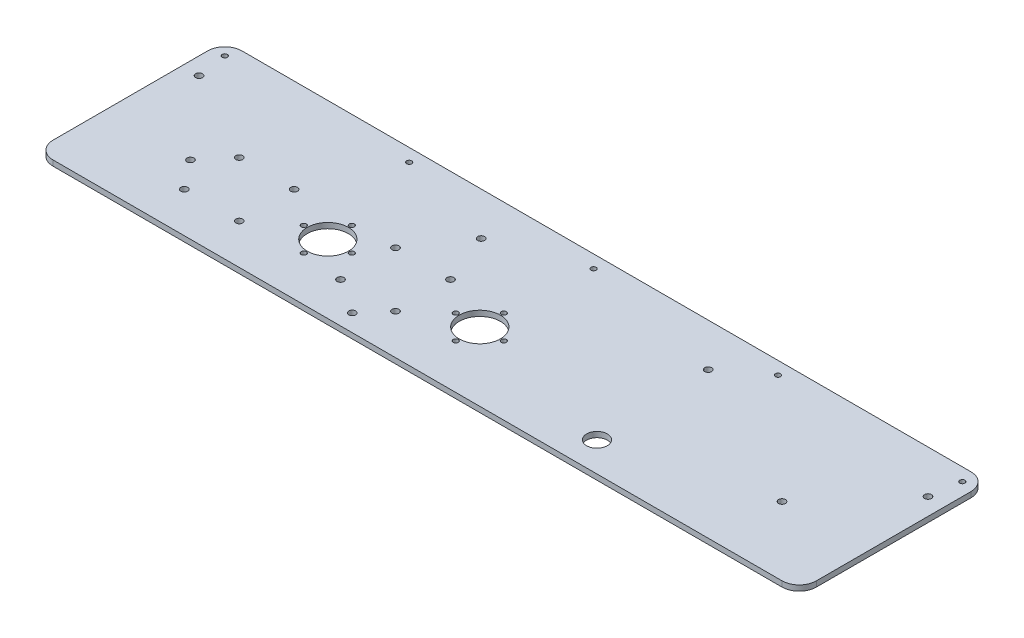
SolidWorks part; units mm, degrees
ref_plane "Front" through (0, 0, 0) normal (0, 0, 1) x (1, 0, 0)
ref_plane "Top" through (0, 0, 0) normal (0, 1, 0) x (1, 0, 0)
ref_plane "Right" through (0, 0, 0) normal (1, 0, 0) x (0, 0, -1)
sketch "Sketch1" plane through (0, 0, 0) normal (0, 1, 0) x (1, 0, 0)
  line L0 (-26.7996, 0) -> (-26.7996, 40)
  line L1 (-26.7996, 0) -> (417.7004, 0)
  line L2 (-26.7996, 0) -> (-26.7996, 110)
  line L3 (-26.7996, 110) -> (417.7004, 110)
  line L4 (417.7004, 0) -> (417.7004, 110)
  line L5 (-26.7996, 40) -> (23.2004, 40)
  line L6 (417.7004, 0) -> (417.7004, 40)
  line L7 (417.7004, 40) -> (367.7004, 40)
  line L8 (23.2004, 40) -> (103.2004, 40)
  line L9 (367.7004, 40) -> (191.7004, 40)
  line L10 (-26.7996, 110) -> (-26.7996, 85)
  line L11 (-26.7996, 85) -> (417.7004, 85)
  line L12 (-26.7996, 85) -> (-16.7996, 85)
  line L13 (417.7004, 85) -> (407.7004, 85)
  line L14 (103.2004, 40) -> (191.7004, 40)
  line L15 (147.4504, 40) -> (147.4504, 85)
  line L16 (279.7004, 40) -> (279.7004, 85)
  line L17 (147.4504, 40) -> (147.4504, 10)
  line L18 (-26.7996, 110) -> (-26.7996, 102.5)
  line L19 (-26.7996, 102.5) -> (417.7004, 102.5)
  line L20 (-26.7996, 102.5) -> (-19.2996, 102.5)
  line L21 (417.7004, 102.5) -> (410.2004, 102.5)
  line L22 (195.4504, 102.5) -> (410.2004, 102.5)
  line L23 (-19.2996, 102.5) -> (195.4504, 102.5)
  line L24 (417.7004, 0) -> (417.7004, 17.2282)
  line L25 (417.7004, 17.2282) -> (282.7004, 17.2282)
  circle A10 centre (367.7004, 40) radius 2
  circle A11 centre (23.2004, 40) radius 2
  circle A12 centre (103.2004, 40) radius 12
  circle A13 centre (103.2004, 40) radius 14
  circle A15 centre (103.2004, 54) radius 1.5
  circle A16 centre (89.2004, 40) radius 1.5
  circle A17 centre (103.2004, 26) radius 1.5
  circle A18 centre (117.2004, 40) radius 1.5
  circle A19 centre (191.7004, 40) radius 12
  circle A20 centre (191.7004, 40) radius 14
  circle A21 centre (191.7004, 26) radius 1.5
  circle A22 centre (205.7004, 40) radius 1.5
  circle A23 centre (191.7004, 54) radius 1.5
  circle A24 centre (177.7004, 40) radius 1.5
  circle A25 centre (-16.7996, 85) radius 2
  circle A26 centre (407.7004, 85) radius 2
  circle A27 centre (147.4504, 85) radius 2
  circle A28 centre (279.7004, 85) radius 2
  circle A29 centre (147.4504, 10) radius 2
  circle A30 centre (195.4504, 102.5) radius 1.5
  circle A31 centre (-19.2996, 102.5) radius 1.5
  circle A32 centre (410.2004, 102.5) radius 1.5
  circle A33 centre (302.8254, 102.5) radius 1.5
  circle A34 centre (88.0754, 102.5) radius 1.5
  circle A35 centre (282.7004, 17.2282) radius 6
  dimension "D3" = 40
  dimension "D7" = 80
  dimension "D8" = 176
  dimension "D9" = 25
  dimension "D11" = 10
  dimension "D12" = 30
  dimension "D13" = 7.5
  dimension "D14" = 7.5
  dimension "D16" = 17.2282
  dimension "D1" = 110
  dimension "D2" = 444.5
  dimension "D4" = 50
  dimension "D5" = 40
  dimension "D6" = 50
  dimension "D10" = 10
  dimension "D15" = 7.5
  dimension "D17" = 135
extrude "Boss-Extrude1" add sketch "Sketch1" along normal blind 3.175 contours A18 L14 A12 L8 A16 A13 A17 | A18 A13 A15 A16 L8 A12 L14 | A24 L14 A19 L9 A22 A20 A23 | A24 A20 A21 A22 L9 A19 L14 | A29 L14 A18 A13 A17 A16 L8 A11 L5 L0 L1 L4 L7 A10 L9 A22 A20 A21 A24 | A28 L11 A27 L15 L14 A24 A20 A23 A22 L9 L16 | A27 L11 A25 L2 L5 A11 L8 A16 A13 A15 A18 L14 L15 | A28 L11 A26 L13 L4 L3 L2 A25 A27 | A28 L16 L9 A10 L7 L4 L13 A26 L11 | A34 L23 A30 L22 A33 A32 L21 L4 L3 L10 L19 A31 region at (196.684, 0, -19.4923) region at (58.5861, 0, -63.184) region at (195.421, 0, -93.7571) region at (195.4504, 0, -106.2666) region at (348.6559, 0, -62.489) region at (93.521, 0, -49.6794) region at (90.515, 0, -38.754) region at (214.7998, 0, -63.4004) region at (204.3858, 0, -41.246) region at (201.3798, 0, -30.3206)
fillet "Fillet1" radius 10 4 edges at (417.7004, 1.5875, -110) (417.7004, 1.5875, 0) (-26.7996, 1.5875, 0) (-26.7996, 1.5875, -110)
sketch "Sketch2" plane through (0, 3.175, 0) normal (0, 1, 0) x (1, 0, 0)
  line L0 (-26.7996, 55.4056) -> (36.2004, 55.4056)
  line L1 (-26.7996, 10) -> (-26.7996, 100) construction
  line L2 (36.2004, 55.4056) -> (68.2004, 55.4056)
  line L3 (-16.7996, 110) -> (407.7004, 110) construction
  line L4 (36.2004, 55.4056) -> (36.2004, 23.4056)
  line L5 (36.2004, 23.4056) -> (68.2004, 23.4056)
  line L6 (68.2004, 55.4056) -> (159.2004, 55.4056)
  line L7 (159.2004, 55.4056) -> (127.2004, 55.4056)
  circle A0 centre (36.2004, 55.4056) radius 2
  circle A1 centre (68.2004, 55.4056) radius 2
  circle A2 centre (36.2004, 23.4056) radius 2
  circle A3 centre (68.2004, 23.4056) radius 2
  circle A4 centre (127.2004, 55.4056) radius 2
  circle A5 centre (159.2004, 55.4056) radius 2
  circle A7 centre (159.2004, 23.4056) radius 2
  circle A8 centre (127.2004, 23.4056) radius 2
  dimension "D5" = 91
  dimension "D6" = 32
  dimension "D1" = 63
  dimension "D2" = 32
  dimension "D3" = 54.5944
  dimension "D4" = 32
extrude "Cut-Extrude1" cut sketch "Sketch2" against normal blind 10 contours A0 | A1 | A2 | A3 | A4 | A8 | A7 | A5
